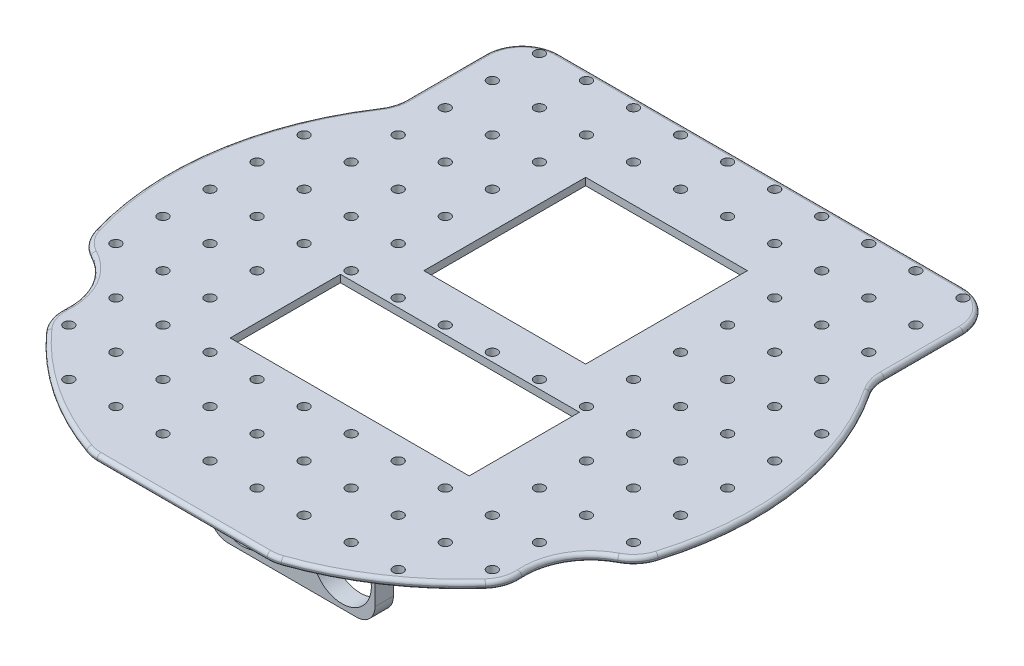
SolidWorks part; units mm, degrees
ref_plane "Front Plane" through (0, 0, 0) normal (0, 0, 1) x (1, 0, 0)
ref_plane "Top Plane" through (0, 0, 0) normal (0, 1, 0) x (1, 0, 0)
ref_plane "Right Plane" through (0, 0, 0) normal (1, 0, 0) x (0, 0, -1)
sketch "Sketch2" plane through (0, 0, 0) normal (0, 1, 0) x (1, 0, 0)
  line L0 (0, 0) -> (0, 108.8103) construction
  line L1 (0, 0) -> (176.5905, 0) construction
sketch "Top_lay" plane through (0, 0, 0) normal (0, 1, 0) x (1, 0, 0)
  line L0 (0, 0) -> (0, 108.8103) construction
  line L1 (-24.7551, -76.0736) -> (24.7551, -76.0736)
  arc A0 (24.7551, -76.0736) -> (-24.7551, -76.0736) centre (0, 0) ccw
  point P3 (0, -76.0223)
  dimension "D1" = 160
extrude "Boss-Extrude2" add sketch "Top_lay" along normal mid plane 2
sketch "Motor_Spacing" plane through (0, 1, 0) normal (0, 1, 0) x (1, 0, 0)
  line L0 (0, 0) -> (0, 108.8103) construction
  line L2 (64.9266, 81.3288) -> (-64.9266, 81.3288)
  line L3 (64.9266, 81.3288) -> (64.9266, 46.3288)
  line L4 (64.9266, 46.3288) -> (-64.9266, 46.3288)
  line L5 (-64.9266, 81.3288) -> (-64.9266, 46.3288)
  line L6 (64.9266, 81.3288) -> (-64.9266, 46.3288) construction
  line L7 (64.9266, 46.3288) -> (-64.9266, 81.3288) construction
  point P2 (0, 63.8288)
  dimension "D1" = 35
extrude "Boss-Extrude6" add sketch "Motor_Spacing" against normal blind 2
sketch "Clamps" plane through (0, 1, 0) normal (0, 1, 0) x (1, 0, 0)
  line L5 (0, 0) -> (0, 108.9952) construction
  line L11 (-64.9266, 81.3288) -> (-71.8617, 81.3288)
  line L12 (-64.9266, 81.3288) -> (-64.9266, 46.8057)
  line L13 (-64.9266, 46.8057) -> (-71.8617, 46.8057)
  line L14 (-71.8617, 81.3288) -> (-71.8617, 46.8057)
  line L15 (64.9266, 46.8057) -> (71.8617, 46.8057)
  line L16 (64.9266, 81.3288) -> (64.9266, 46.8057)
  line L17 (64.9266, 81.3288) -> (71.8617, 81.3288)
  line L18 (71.8617, 81.3288) -> (71.8617, 46.8057)
sketch "RPi_L298N_hatch" plane through (0, -1, 0) normal (0, -1, 0) x (1, 0, 0)
  line L0 (0, 0) -> (0, -108.8103) construction
  line L1 (-32.5, 0.5353) -> (32.5, 0.5353)
  line L2 (-32.5, 0.5353) -> (-32.5, 30.5353)
  line L3 (-32.5, 30.5353) -> (32.5, 30.5353)
  line L4 (32.5, 0.5353) -> (32.5, 30.5353)
  line L5 (-32.5, 0.5353) -> (32.5, 30.5353) construction
  line L6 (-32.5, 30.5353) -> (32.5, 0.5353) construction
  line L8 (-22, -11.6596) -> (22, -11.6596)
  line L9 (-22, -11.6596) -> (-22, -55.6596)
  line L10 (-22, -55.6596) -> (22, -55.6596)
  line L11 (22, -11.6596) -> (22, -55.6596)
  line L12 (-22, -11.6596) -> (22, -55.6596) construction
  line L13 (-22, -55.6596) -> (22, -11.6596) construction
  point P0 (0, 15.5353)
  point P7 (0, -33.6596)
  point P12 (0, -89.9264)
  dimension "D1" = 65
  dimension "D2" = 30
  dimension "D3" = 44
  dimension "D4" = 44
sketch "PIR_ULTRA" plane through (0, -1, 0) normal (0, -1, 0) x (1, 0, 0)
  line L0 (0, 0) -> (0, -108.8103) construction
  line L12 (22.5, 46.1285) -> (-22.5, 46.1285)
  line L13 (22.5, 46.1285) -> (22.5, 41.1285)
  line L18 (22.5, 41.1285) -> (-22.5, 41.1285)
  line L19 (-22.5, 46.1285) -> (-22.5, 41.1285)
  line L20 (22.5, 46.1285) -> (-22.5, 41.1285) construction
  line L21 (22.5, 41.1285) -> (-22.5, 46.1285) construction
  point P0 (0, 43.6285)
  point P7 (0, 43.6285)
  dimension "D1" = 5
  dimension "D2" = 45
extrude "Boss-Extrude10" add sketch "PIR_ULTRA" along normal blind 31
sketch "Sketch4" plane through (0, 1, 0) normal (0, 1, 0) x (1, 0, 0)
  line L0 (30.9083, 77.9119) -> (33.3167, 77.8645) construction
  line L5 (-70.5204, 79.9042) -> (-69.9756, 79.8935) construction
  line L6 (-70.5204, 77.1986) -> (-69.9756, 77.2093) construction
  line L7 (30.9083, 79.1909) -> (33.3167, 79.2382) construction
  line L8 (-31.8745, -49.4486) -> (-31.8745, -62.2486) construction
  line L9 (-58.2826, 77.4389) -> (-56.6233, 77.4715) construction
  line L10 (-58.2826, 79.6638) -> (-56.6233, 79.6312) construction
  line L11 (-45.7424, 79.4175) -> (-43.5734, 79.3749) construction
  line L12 (-45.7424, 77.6853) -> (-43.5734, 77.7279) construction
  line L13 (-33.1029, 77.9335) -> (-30.6228, 77.9823) construction
  line L14 (-33.1029, 79.1692) -> (-30.6228, 79.1205) construction
  line L15 (-20.3992, 78.9197) -> (-17.7363, 78.8674) construction
  line L16 (-20.3992, 78.1831) -> (-17.7363, 78.2354) construction
  line L17 (-7.6444, 78.6691) -> (-4.901, 78.6152) construction
  line L18 (-7.6444, 78.4336) -> (-4.901, 78.4875) construction
  line L19 (5.157, 78.6851) -> (7.8877, 78.7387) construction
  line L20 (5.157, 78.4177) -> (7.8877, 78.364) construction
  line L21 (18.0058, 78.1653) -> (20.629, 78.1138) construction
  line L22 (18.0058, 78.9375) -> (20.629, 78.989) construction
  line L23 (56.9741, 77.3998) -> (58.4311, 77.3712) construction
  line L24 (56.9741, 79.7029) -> (58.4311, 79.7315) construction
  line L25 (43.8811, 79.4457) -> (45.934, 79.4861) construction
  line L26 (43.8811, 77.657) -> (45.934, 77.6167) construction
  line L31 (-31.8745, -62.2486) -> (-31.8745, -55.8486) construction
  line L32 (-31.8745, -55.8486) -> (32.1255, -55.8486) construction
  circle A1 centre (-70.2745, 78.5514) radius 1.375
  circle A2 centre (-57.4745, 78.5514) radius 1.375
  circle A3 centre (-44.6745, 78.5514) radius 1.375
  circle A4 centre (-31.8745, 78.5514) radius 1.375
  circle A5 centre (-19.0745, 78.5514) radius 1.375
  circle A6 centre (-6.2745, 78.5514) radius 1.375
  circle A7 centre (6.5255, 78.5514) radius 1.375
  circle A8 centre (19.3255, 78.5514) radius 1.375
  circle A9 centre (32.1255, 78.5514) radius 1.375
  circle A10 centre (44.9255, 78.5514) radius 1.375
  circle A11 centre (57.7255, 78.5514) radius 1.375
  circle A12 centre (70.5255, 78.5514) radius 1.375
  circle A13 centre (-57.4745, 65.7514) radius 1.375
  circle A14 centre (-44.6745, 65.7514) radius 1.375
  circle A15 centre (-31.8745, 65.7514) radius 1.375
  circle A16 centre (-19.0745, 65.7514) radius 1.375
  circle A17 centre (-6.2745, 65.7514) radius 1.375
  circle A18 centre (6.5255, 65.7514) radius 1.375
  circle A19 centre (19.3255, 65.7514) radius 1.375
  circle A20 centre (32.1255, 65.7514) radius 1.375
  circle A21 centre (44.9255, 65.7514) radius 1.375
  circle A22 centre (57.7255, 65.7514) radius 1.375
  circle A23 centre (70.5255, 65.7514) radius 1.375
  circle A24 centre (-57.4745, 52.9514) radius 1.375
  circle A25 centre (-44.6745, 52.9514) radius 1.375
  circle A26 centre (-31.8745, 52.9514) radius 1.375
  circle A27 centre (-19.0745, 52.9514) radius 1.375
  circle A28 centre (-6.2745, 52.9514) radius 1.375
  circle A29 centre (6.5255, 52.9514) radius 1.375
  circle A30 centre (19.3255, 52.9514) radius 1.375
  circle A31 centre (32.1255, 52.9514) radius 1.375
  circle A32 centre (44.9255, 52.9514) radius 1.375
  circle A33 centre (57.7255, 52.9514) radius 1.375
  circle A34 centre (70.5255, 52.9514) radius 1.375
  circle A35 centre (-57.4745, 40.1514) radius 1.375
  circle A36 centre (-44.6745, 40.1514) radius 1.375
  circle A37 centre (-31.8745, 40.1514) radius 1.375
  circle A38 centre (-19.0745, 40.1514) radius 1.375
  circle A39 centre (-6.2745, 40.1514) radius 1.375
  circle A40 centre (6.5255, 40.1514) radius 1.375
  circle A41 centre (19.3255, 40.1514) radius 1.375
  circle A42 centre (32.1255, 40.1514) radius 1.375
  circle A43 centre (44.9255, 40.1514) radius 1.375
  circle A44 centre (57.7255, 40.1514) radius 1.375
  circle A46 centre (-57.4745, 27.3514) radius 1.375
  circle A47 centre (-44.6745, 27.3514) radius 1.375
  circle A48 centre (-31.8745, 27.3514) radius 1.375
  circle A49 centre (-19.0745, 27.3514) radius 1.375
  circle A50 centre (-6.2745, 27.3514) radius 1.375
  circle A51 centre (6.5255, 27.3514) radius 1.375
  circle A52 centre (19.3255, 27.3514) radius 1.375
  circle A53 centre (32.1255, 27.3514) radius 1.375
  circle A54 centre (44.9255, 27.3514) radius 1.375
  circle A55 centre (57.7255, 27.3514) radius 1.375
  circle A56 centre (70.5255, 27.3514) radius 1.375
  circle A57 centre (-57.4745, 14.5514) radius 1.375
  circle A58 centre (-44.6745, 14.5514) radius 1.375
  circle A59 centre (-31.8745, 14.5514) radius 1.375
  circle A60 centre (-19.0745, 14.5514) radius 1.375
  circle A61 centre (-6.2745, 14.5514) radius 1.375
  circle A62 centre (6.5255, 14.5514) radius 1.375
  circle A63 centre (19.3255, 14.5514) radius 1.375
  circle A64 centre (32.1255, 14.5514) radius 1.375
  circle A65 centre (44.9255, 14.5514) radius 1.375
  circle A66 centre (57.7255, 14.5514) radius 1.375
  circle A67 centre (70.5255, 14.5514) radius 1.375
  circle A68 centre (-57.4745, 1.7514) radius 1.375
  circle A69 centre (-44.6745, 1.7514) radius 1.375
  circle A70 centre (-31.8745, 1.7514) radius 1.375
  circle A71 centre (-19.0745, 1.7514) radius 1.375
  circle A72 centre (-6.2745, 1.7514) radius 1.375
  circle A73 centre (6.5255, 1.7514) radius 1.375
  circle A74 centre (19.3255, 1.7514) radius 1.375
  circle A75 centre (32.1255, 1.7514) radius 1.375
  circle A76 centre (44.9255, 1.7514) radius 1.375
  circle A77 centre (57.7255, 1.7514) radius 1.375
  circle A78 centre (70.5255, 1.7514) radius 1.375
  circle A79 centre (-57.4745, -11.0486) radius 1.375
  circle A80 centre (-44.6745, -11.0486) radius 1.375
  circle A82 centre (-19.0745, -11.0486) radius 1.375
  circle A83 centre (-6.2745, -11.0486) radius 1.375
  circle A84 centre (6.5255, -11.0486) radius 1.375
  circle A85 centre (19.3255, -11.0486) radius 1.375
  circle A87 centre (44.9255, -11.0486) radius 1.375
  circle A88 centre (57.7255, -11.0486) radius 1.375
  circle A89 centre (70.5255, -11.0486) radius 1.375
  circle A90 centre (-57.4745, -23.8486) radius 1.375
  circle A91 centre (-44.6745, -23.8486) radius 1.375
  circle A93 centre (-19.0745, -23.8486) radius 1.375
  circle A94 centre (-6.2745, -23.8486) radius 1.375
  circle A95 centre (6.5255, -23.8486) radius 1.375
  circle A96 centre (19.3255, -23.8486) radius 1.375
  circle A98 centre (44.9255, -23.8486) radius 1.375
  circle A99 centre (57.7255, -23.8486) radius 1.375
  circle A100 centre (70.5255, -23.8486) radius 1.375
  circle A101 centre (-57.4745, -36.6486) radius 1.375
  circle A102 centre (-44.6745, -36.6486) radius 1.375
  circle A103 centre (-31.8745, -36.6486) radius 1.375
  circle A104 centre (-19.0745, -36.6486) radius 1.375
  circle A105 centre (-6.2745, -36.6486) radius 1.375
  circle A106 centre (6.5255, -36.6486) radius 1.375
  circle A107 centre (19.3255, -36.6486) radius 1.375
  circle A108 centre (32.1255, -36.6486) radius 1.375
  circle A109 centre (44.9255, -36.6486) radius 1.375
  circle A110 centre (57.7255, -36.6486) radius 1.375
  circle A111 centre (70.5255, -36.6486) radius 1.375
  circle A112 centre (-57.4745, -49.4486) radius 1.375
  circle A113 centre (-44.6745, -49.4486) radius 1.375
  circle A114 centre (-31.8745, -49.4486) radius 1.375
  circle A115 centre (-19.0745, -49.4486) radius 1.375
  circle A116 centre (-6.2745, -49.4486) radius 1.375
  circle A117 centre (6.5255, -49.4486) radius 1.375
  circle A118 centre (19.3255, -49.4486) radius 1.375
  circle A119 centre (32.1255, -49.4486) radius 1.375
  circle A120 centre (44.9255, -49.4486) radius 1.375
  circle A121 centre (57.7255, -49.4486) radius 1.375
  circle A122 centre (70.5255, -49.4486) radius 1.375
  circle A123 centre (-57.4745, -62.2486) radius 1.375
  circle A124 centre (-44.6745, -62.2486) radius 1.375
  circle A125 centre (-31.8745, -62.2486) radius 1.375
  circle A130 centre (32.1255, -62.2486) radius 1.375
  circle A131 centre (44.9255, -62.2486) radius 1.375
  circle A132 centre (57.7255, -62.2486) radius 1.375
  circle A133 centre (70.5255, -62.2486) radius 1.375
  circle A134 centre (-57.4745, -75.0486) radius 1.375
  circle A135 centre (-44.6745, -75.0486) radius 1.375
  circle A136 centre (-31.8745, -75.0486) radius 1.375
  circle A141 centre (32.1255, -75.0486) radius 1.375
  circle A142 centre (44.9255, -75.0486) radius 1.375
  circle A143 centre (57.7255, -75.0486) radius 1.375
  circle A144 centre (70.5255, -75.0486) radius 1.375
  circle A145 centre (-70.2745, 65.7514) radius 1.375
  circle A146 centre (-70.2745, 52.9514) radius 1.375
  circle A148 centre (-70.2745, 27.3514) radius 1.375
  circle A149 centre (-70.2745, 14.5514) radius 1.375
  circle A150 centre (-70.2745, 1.7514) radius 1.375
  circle A151 centre (-70.2745, -11.0486) radius 1.375
  circle A152 centre (-70.2745, -23.8486) radius 1.375
  circle A153 centre (-70.2745, -36.6486) radius 1.375
  circle A154 centre (-70.2745, -49.4486) radius 1.375
  circle A155 centre (-70.2745, -62.2486) radius 1.375
  circle A156 centre (-70.2745, -75.0486) radius 1.375
  circle A157 centre (-6.2745, -62.2486) radius 1.375 [skipped]
  circle A158 centre (6.5255, -62.2486) radius 1.375 [skipped]
  circle A159 centre (-19.0745, -62.2486) radius 1.375 [skipped]
  circle A160 centre (19.3255, -62.2486) radius 1.375 [skipped]
  circle A161 centre (-19.0745, -75.0486) radius 1.375 [skipped]
  circle A162 centre (-6.2745, -75.0486) radius 1.375 [skipped]
  circle A163 centre (6.5255, -75.0486) radius 1.375 [skipped]
  circle A164 centre (19.3255, -75.0486) radius 1.375 [skipped]
  circle A165 centre (19.3255, -62.2486) radius 1.375
  circle A166 centre (6.5255, -62.2486) radius 1.375
  circle A167 centre (-6.2745, -62.2486) radius 1.375
  circle A168 centre (-19.0745, -62.2486) radius 1.375
  circle A169 centre (-70.2745, 40.1514) radius 1.375 [skipped]
  circle A170 centre (70.5255, 40.1514) radius 1.375 [skipped]
  circle A171 centre (-31.8745, -11.0486) radius 1.375 [skipped]
  circle A172 centre (-31.8745, -23.8486) radius 1.375 [skipped]
  circle A173 centre (32.1255, -11.0486) radius 1.375 [skipped]
  circle A174 centre (32.1255, -23.8486) radius 1.375 [skipped]
  point P0 (-1.6495, 78.5514)
  dimension "D4" = 12
  dimension "D5" = 13
extrude "Cut-Extrude5" cut sketch "Sketch4" against normal blind 10
sketch "Sketch5" plane through (0, 0, 46.1285) normal (0, 0, 1) x (1, 0, 0)
  line L5 (22.5, -32) -> (-22.5, -32) construction
  line L6 (0, 0) -> (0, -32) construction
  circle A0 centre (-13.5, -22.8039) radius 8
  circle A1 centre (13.5, -22.8039) radius 8
  point P0 (-13.5, -22.8039)
  dimension "D3" = 16
  dimension "D2" = 27
extrude "Cut-Extrude6" cut sketch "Sketch5" against normal blind 10
extrude "Cut-Extrude7" cut sketch "RPi_L298N_hatch" against normal blind 10
sketch "Sketch6" plane through (0, 1, 0) normal (0, 1, 0) x (1, 0, 0)
  line L0 (0, 0) -> (0, -19.09) construction
  arc A0 (-62.8037, -49.555) -> (-75.0034, -27.8295) centre (-79.7663, -44.7922) ccw
  arc A1 (-70.3887, -38.0189) -> (-24.7551, -76.0736) centre (0, 0) ccw construction
  arc A2 (-64.9266, 46.739) -> (-71.4634, -35.958) centre (0, 0) ccw construction
  arc A3 (-75.0034, -27.8295) -> (-62.8037, -49.555) centre (0, 0) ccw
  arc A4 (62.8037, -49.555) -> (75.0034, -27.8295) centre (79.7663, -44.7922) cw
  arc A5 (75.0034, -27.8295) -> (62.8037, -49.555) centre (0, 0) cw
extrude "Cut-Extrude8" cut sketch "Sketch6" against normal blind 10 contours A0 A3 | A5 A4 region at (-67.4143, 1, 37.856) region at (67.4143, 1, 37.856)
fillet "Fillet1" radius 10 10 edges at (-75.0034, 0, 27.8295) (-62.8037, 0, 49.555) (-24.7551, 0, 76.0736) (24.7551, 0, 76.0736) (62.8037, 0, 49.555) (75.0034, 0, 27.8295) (64.9266, 0, -46.739) (64.9266, 0, -81.3288) (-64.9266, 0, -81.3288) (-64.9266, 0, -46.739)
fillet "Fillet2" radius 5 2 edges at (-22.5, -32, 43.6285) (22.5, -32, 43.6285)
fillet "Fillet3" radius 1 4 edges at (-22.5, -1, 43.6285) (0, -1, 41.1285) (22.5, -1, 43.6285) (0, -1, 46.1285)
fillet "Fillet4" radius 1 40 edges at (-61.6652, 1, 49.8808) (-44.453, 1, 66.5126) (-24.7893, 1, 75.9323) (0, 1, 76.0736) (24.7893, 1, 75.9323) (44.453, 1, 66.5126) (61.6652, 1, 49.8808) (64.4041, 1, 36.1656) (74.689, 1, 26.688) (79.144, 1, -11.6716) (65.3545, 1, -46.966) (64.9266, 1, -60.5943) (61.9977, 1, -78.3998) (0, 1, -81.3288) (-61.9977, 1, -78.3998) (-64.9266, 1, -60.5943) (-65.3545, 1, -46.966) (-79.144, 1, -11.6716) (-74.689, 1, 26.688) (-65.3545, -1, -46.966) (-64.9266, -1, -60.5943) (-61.9977, -1, -78.3998) (0, -1, -81.3288) (61.9977, -1, -78.3998) (64.9266, -1, -60.5943) (65.3545, -1, -46.966) (79.144, -1, -11.6716) (74.689, -1, 26.688) (64.4041, -1, 36.1656) (61.6652, -1, 49.8808) (44.453, -1, 66.5126) (24.7893, -1, 75.9323) (0, -1, 76.0736) (-24.7893, -1, 75.9323) (-44.453, -1, 66.5126) (-61.6652, -1, 49.8808) (-64.4041, -1, 36.1656) (-74.689, -1, 26.688) (-64.4041, 1, 36.1656) (-79.144, -1, -11.6716)
